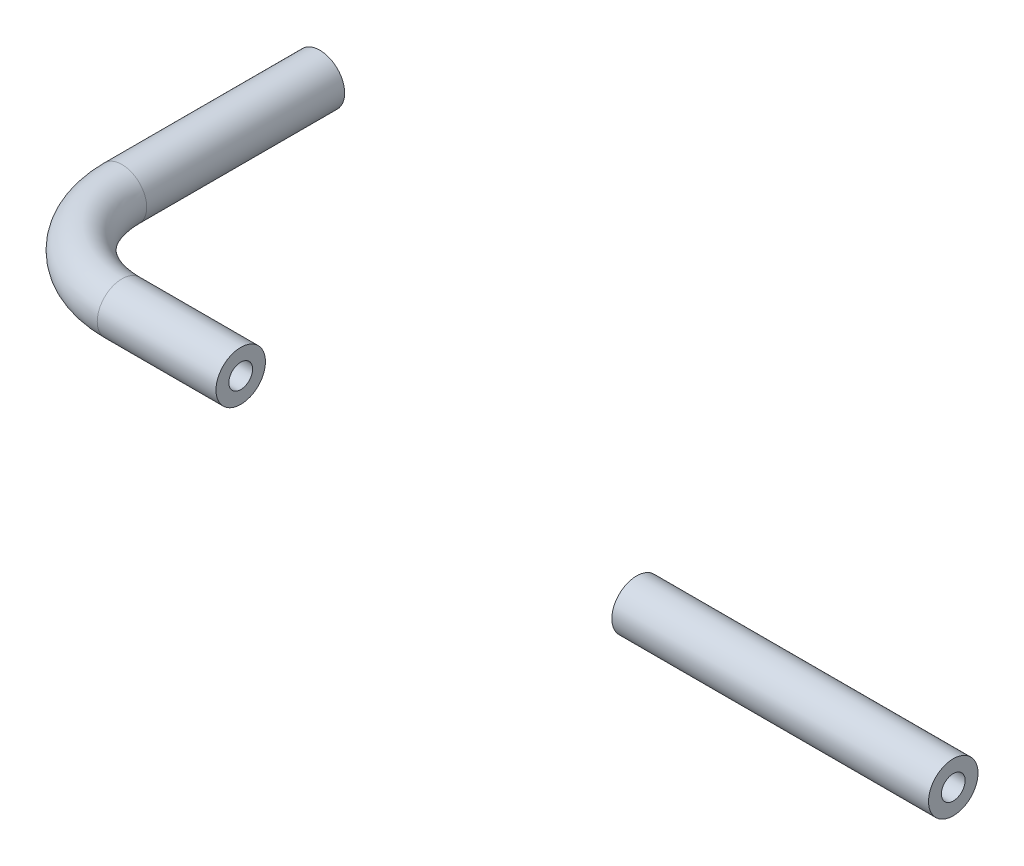
SolidWorks part; units mm, degrees
ref_plane "Front Plane" through (0, 0, 0) normal (0, 0, 1) x (1, 0, 0)
ref_plane "Top Plane" through (0, 0, 0) normal (0, 1, 0) x (1, 0, 0)
ref_plane "Right Plane" through (0, 0, 0) normal (1, 0, 0) x (0, 0, -1)
sketch "Sketch1" plane through (0, 0, 0) normal (0, 1, 0) x (1, 0, 0)
  line L0 (-27.94, 38.1) -> (-27.94, 12.7)
  line L1 (-15.24, 0) -> (0, 0)
  arc A0 (-27.94, 12.7) -> (-15.24, 0) centre (-15.24, 12.7) ccw
  dimension "D1" = 12.7
  dimension "D2" = 38.1
  dimension "D3" = 27.94
sweep "Sweep-Thin1" add path "Sketch1" circular profile diameter 6.35 parameters "D1"=1.651, "D3"=6.35
sketch "Sketch15" plane through (0, 0, 0) normal (0, 1, 0) x (1, 0, 0)
  line L0 (50.8, 0) -> (91.44, 0)
  dimension "D1" = 50.8
  dimension "D2" = 40.64
sweep "Sweep-Thin2" add path "Sketch15" circular profile diameter 6.35 parameters "D1"=1.651, "D3"=6.35
